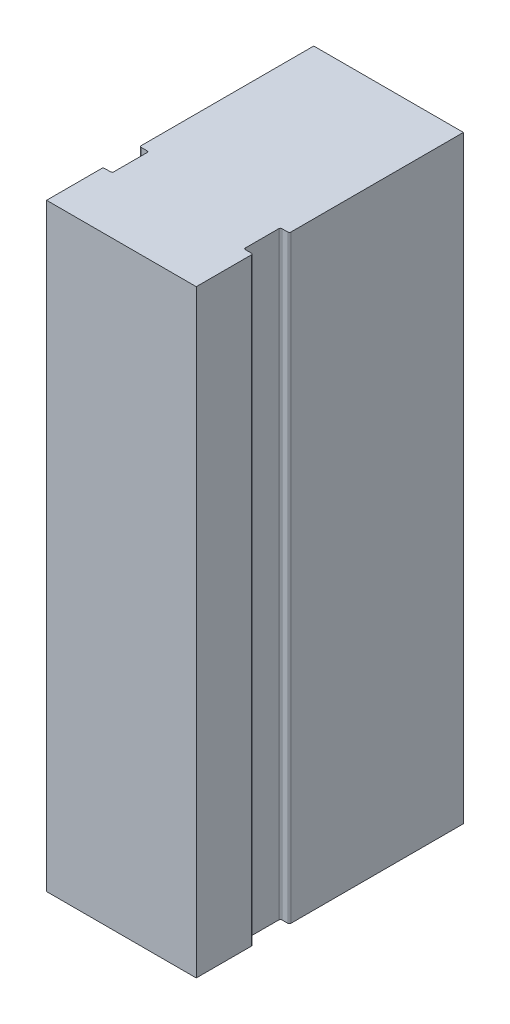
SolidWorks part; units mm, degrees
ref_plane "Front Plane" through (0, 0, 0) normal (0, 0, 1) x (1, 0, 0)
ref_plane "Top Plane" through (0, 0, 0) normal (0, 1, 0) x (1, 0, 0)
ref_plane "Right Plane" through (0, 0, 0) normal (1, 0, 0) x (0, 0, -1)
sketch "Sketch1" plane through (0, 0, 0) normal (0, 0, 1) x (1, 0, 0)
  line L1 (0, 0) -> (25.4, 0)
  line L2 (0, 0) -> (0, 101.6)
  line L3 (0, 101.6) -> (25.4, 101.6)
  line L4 (25.4, 0) -> (25.4, 101.6)
  dimension "D1" = 25.4
  dimension "D2" = 101.6
extrude "Boss-Extrude1" add sketch "Sketch1" along normal up to surface (45.339 mm away)
ref_plane "Plane1" through (12.7, 0, 0) normal (-1, 0, 0) x (0, 0, 1)
sketch "Sketch2" plane through (0, 101.6, 0) normal (0, 1, 0) x (1, 0, 0)
  line L0 (25.4, -29.2862) -> (25.4, -35.9918)
  line L1 (0, -29.2862) -> (0, -35.9918)
  line L14 (33.3248, -20.447) -> (32.8168, -19.939)
  line L15 (32.8168, -19.939) -> (25.908, -19.939)
  line L16 (25.908, -19.939) -> (25.4, -20.447)
  line L17 (25.4, -20.447) -> (25.4, -29.2862)
  line L18 (25.146, -29.5402) -> (24.13, -29.5402)
  line L19 (23.876, -29.7942) -> (23.876, -35.4838)
  line L20 (24.13, -35.7378) -> (25.146, -35.7378)
  line L21 (25.4, -35.9918) -> (25.4, -45.339)
  line L22 (25.4, -45.339) -> (29.3624, -49.3014)
  line L23 (29.3624, -49.3014) -> (29.3624, -71.8312)
  line L24 (29.3624, -71.8312) -> (29.8704, -72.3392)
  line L25 (29.8704, -72.3392) -> (32.8168, -72.3392)
  line L26 (32.8168, -72.3392) -> (33.3248, -71.8312)
  line L27 (33.3248, -71.8312) -> (33.3248, -20.447)
  line L28 (33.3248, -20.447) -> (32.8168, -19.939) construction
  line L29 (32.8168, -19.939) -> (25.908, -19.939) construction
  line L30 (25.908, -19.939) -> (25.4, -20.447) construction
  line L31 (25.4, -20.447) -> (25.4, -29.2862)
  line L32 (25.146, -29.5402) -> (24.13, -29.5402)
  line L33 (23.876, -29.7942) -> (23.876, -35.4838)
  line L34 (24.13, -35.7378) -> (25.146, -35.7378)
  line L35 (25.4, -35.9918) -> (25.4, -45.339) construction
  line L36 (25.4, -45.339) -> (29.3624, -49.3014) construction
  line L37 (29.3624, -49.3014) -> (29.3624, -71.8312) construction
  line L38 (29.3624, -71.8312) -> (29.8704, -72.3392) construction
  line L39 (29.8704, -72.3392) -> (32.8168, -72.3392) construction
  line L40 (32.8168, -72.3392) -> (33.3248, -71.8312) construction
  line L41 (33.3248, -71.8312) -> (33.3248, -20.447) construction
  line L42 (0, -29.2862) -> (0, -20.447)
  line L43 (0, -20.447) -> (-0.508, -19.939)
  line L44 (-0.508, -19.939) -> (-7.4168, -19.939)
  line L45 (-7.4168, -19.939) -> (-7.9248, -20.447)
  line L46 (-7.9248, -20.447) -> (-7.9248, -71.8312)
  line L47 (-7.9248, -71.8312) -> (-7.4168, -72.3392)
  line L48 (-7.4168, -72.3392) -> (-4.4704, -72.3392)
  line L49 (-4.4704, -72.3392) -> (-3.9624, -71.8312)
  line L50 (-3.9624, -71.8312) -> (-3.9624, -49.3014)
  line L51 (-3.9624, -49.3014) -> (0, -45.339)
  line L52 (0, -45.339) -> (0, -35.9918)
  line L53 (0.254, -35.7378) -> (1.27, -35.7378)
  line L54 (1.524, -35.4838) -> (1.524, -29.7942)
  line L55 (1.27, -29.5402) -> (0.254, -29.5402)
  line L56 (0, -29.2862) -> (0, -20.447)
  line L57 (0, -20.447) -> (-0.508, -19.939) construction
  line L58 (-0.508, -19.939) -> (-7.4168, -19.939) construction
  line L59 (-7.4168, -19.939) -> (-7.9248, -20.447) construction
  line L60 (-7.9248, -20.447) -> (-7.9248, -71.8312) construction
  line L61 (-7.9248, -71.8312) -> (-7.4168, -72.3392) construction
  line L62 (-7.4168, -72.3392) -> (-4.4704, -72.3392) construction
  line L63 (-4.4704, -72.3392) -> (-3.9624, -71.8312) construction
  line L64 (-3.9624, -71.8312) -> (-3.9624, -49.3014) construction
  line L65 (-3.9624, -49.3014) -> (0, -45.339) construction
  line L66 (0, -45.339) -> (0, -35.9918) construction
  line L67 (0.254, -35.7378) -> (1.27, -35.7378)
  line L68 (1.524, -35.4838) -> (1.524, -29.7942)
  line L69 (1.27, -29.5402) -> (0.254, -29.5402)
  arc A4 (25.146, -29.5402) -> (25.4, -29.2862) centre (25.146, -29.2862) ccw
  arc A5 (24.13, -29.5402) -> (23.876, -29.7942) centre (24.13, -29.7942) ccw
  arc A6 (23.876, -35.4838) -> (24.13, -35.7378) centre (24.13, -35.4838) ccw
  arc A7 (25.4, -35.9918) -> (25.146, -35.7378) centre (25.146, -35.9918) ccw
  arc A8 (25.146, -29.5402) -> (25.4, -29.2862) centre (25.146, -29.2862) ccw
  arc A9 (24.13, -29.5402) -> (23.876, -29.7942) centre (24.13, -29.7942) ccw
  arc A10 (23.876, -35.4838) -> (24.13, -35.7378) centre (24.13, -35.4838) ccw
  arc A11 (25.4, -35.9918) -> (25.146, -35.7378) centre (25.146, -35.9918) ccw
  arc A12 (0.254, -35.7378) -> (0, -35.9918) centre (0.254, -35.9918) ccw
  arc A13 (1.27, -35.7378) -> (1.524, -35.4838) centre (1.27, -35.4838) ccw
  arc A14 (1.524, -29.7942) -> (1.27, -29.5402) centre (1.27, -29.7942) ccw
  arc A15 (0, -29.2862) -> (0.254, -29.5402) centre (0.254, -29.2862) ccw
  arc A16 (0.254, -35.7378) -> (0, -35.9918) centre (0.254, -35.9918) ccw
  arc A17 (1.27, -35.7378) -> (1.524, -35.4838) centre (1.27, -35.4838) ccw
  arc A18 (1.524, -29.7942) -> (1.27, -29.5402) centre (1.27, -29.7942) ccw
  arc A19 (0, -29.2862) -> (0.254, -29.5402) centre (0.254, -29.2862) ccw
  line M38 (25.4, -45.339) -> (25.4, 0)
  line M40 (0, 0) -> (0, -45.339)
  dimension "D1" = 0
  dimension "D2" = 0
extrude "Cut-Extrude1" cut sketch "Sketch2" against normal through all contours A19 A16 L67 A17 L68 A18 L69 M40 | A11 A8 L32 A9 L33 A10 L34 M38 region at (24.6421, 101.6, 32.639) region at (0.7579, 101.6, 32.639)
